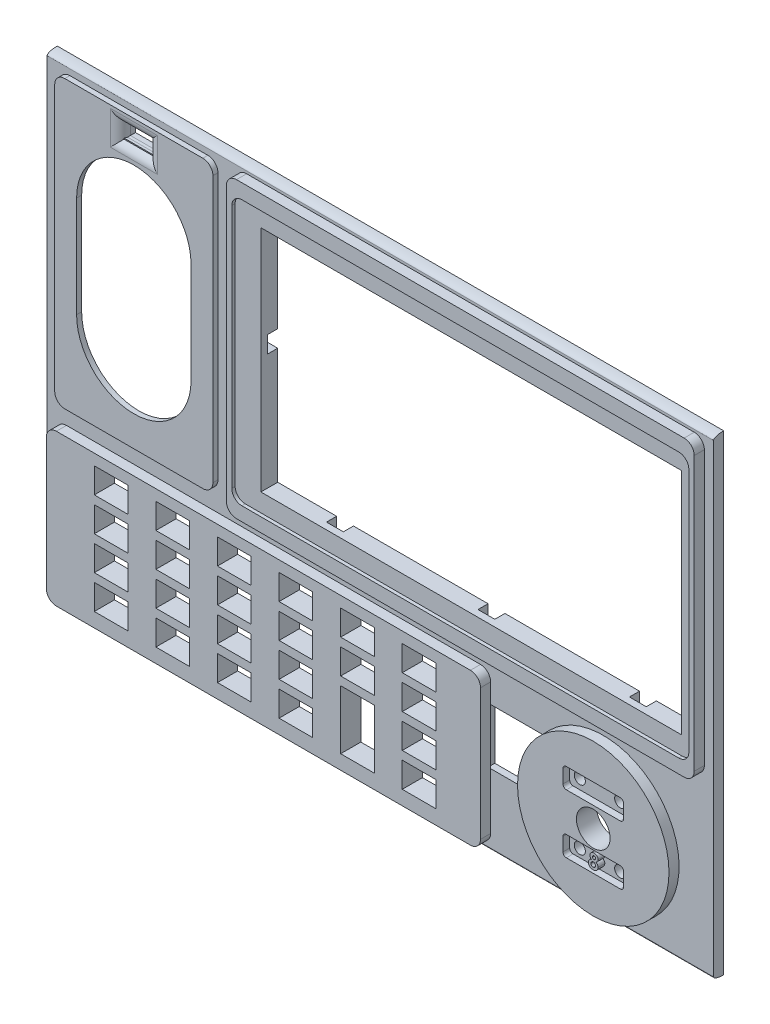
SolidWorks part; units mm, degrees
ref_plane "Front Plane" through (0, 0, 0) normal (0, 0, 1) x (1, 0, 0)
ref_plane "Top Plane" through (0, 0, 0) normal (0, 1, 0) x (1, 0, 0)
ref_plane "Right Plane" through (0, 0, 0) normal (1, 0, 0) x (0, 0, -1)
sketch "Sketch1" plane through (0, 0, 0) normal (0, 0, 1) x (1, 0, 0)
  line L1 (99, -70) -> (-99, -70)
  line L2 (99, -70) -> (99, 70)
  line L3 (99, 70) -> (-99, 70)
  line L4 (-99, -70) -> (-99, 70)
  line L5 (99, -70) -> (-99, 70) construction
  line L6 (99, 70) -> (-99, -70) construction
  point P0 (0, 0)
  dimension "D1" = 198
  dimension "D2" = 140
extrude "main_body" add sketch "Sketch1" along normal blind 3
fillet "long_corners" radius 3 2 edges at (0, 70, 3) (0, -70, 3) second distance 1 first distance on face at (0, 70, 1.5) first distance on face at (0, -70, 1.5)
sketch "Sketch2" plane through (0, 0, 3) normal (0, 0, 1) x (1, 0, 0)
  line L0 (-99, 24.75) -> (99, 24.75) construction
  line L1 (-99, 69) -> (-99, -69) construction
  line L2 (99, -69) -> (99, 69) construction
  line L3 (99, 69) -> (-99, 69) construction
  line L4 (-48.25, -17.75) -> (-95.25, -17.75)
  line L5 (-48.25, -17.75) -> (-48.25, 67.25)
  line L6 (-48.25, 67.25) -> (-95.25, 67.25)
  line L7 (-95.25, -17.75) -> (-95.25, 67.25)
  line L8 (-48.25, -17.75) -> (-95.25, 67.25) construction
  line L9 (-48.25, 67.25) -> (-95.25, -17.75) construction
  point P6 (-71.75, 24.75)
  dimension "D1" = 85
  dimension "D2" = 47
  dimension "D3" = 27.25
  dimension "D4" = 44.25
extrude "speaker" add sketch "Sketch2" along normal blind 1.5
fillet "speaker_corners" radius 3 4 edges at (-95.25, 67.25, 3.75) (-95.25, -17.75, 3.75) (-48.25, -17.75, 3.75) (-48.25, 67.25, 3.75)
sketch "Sketch19" plane through (0, 0, 4.5) normal (0, 0, 1) x (1, 0, 0)
  line L0 (-71.75, 67.25) -> (-71.75, -17.75) construction
  line L1 (-51.25, 67.25) -> (-92.25, 67.25) construction
  line L2 (-92.25, -17.75) -> (-51.25, -17.75) construction
  line L3 (-71.75, 8.25) -> (-71.75, 38.25) construction
  line L4 (-95.25, 64.25) -> (-95.25, -14.75) construction
  line L5 (-95.25, 24.75) -> (-48.25, 24.75) construction
  line L6 (-48.25, -14.75) -> (-48.25, 64.25) construction
  line L7 (-88.75, 8.25) -> (-88.75, 38.25)
  line L8 (-54.75, 8.25) -> (-54.75, 38.25)
  arc A0 (-88.75, 8.25) -> (-54.75, 8.25) centre (-71.75, 8.25) ccw
  arc A1 (-54.75, 38.25) -> (-88.75, 38.25) centre (-71.75, 38.25) ccw
  point P14 (-71.75, 23.25)
  point P19 (-71.75, -8.75)
  point P20 (-71.75, 55.25)
  dimension "D2" = 64
  dimension "D1" = 34
  dimension "D3" = 12
extrude "speaker_cut" cut sketch "Sketch19" against normal through all
sketch "Sketch21" plane through (0, 0, 0) normal (0, 0, -1) x (-1, 0, 0)
  line L0 (71.75, -8.75) -> (71.75, 55.25) construction
  line L2 (54.75, 8.25) -> (54.75, 38.25) construction
  line L3 (54.75, 23.25) -> (88.75, 23.25) construction
  line L4 (88.75, 38.25) -> (88.75, 8.25) construction
  line L5 (50.25, 59.25) -> (93.25, 59.25)
  line L6 (50.25, 59.25) -> (50.25, -12.75)
  line L7 (50.25, -12.75) -> (93.25, -12.75)
  line L8 (93.25, 59.25) -> (93.25, -12.75)
  line L9 (50.25, 59.25) -> (93.25, -12.75) construction
  line L10 (50.25, -12.75) -> (93.25, 59.25) construction
  arc A0 (54.75, 8.25) -> (88.75, 8.25) centre (71.75, 8.25) ccw construction
  arc A1 (88.75, 38.25) -> (54.75, 38.25) centre (71.75, 38.25) ccw construction
  point P14 (71.75, 23.25)
  dimension "D1" = 43
  dimension "D2" = 72
extrude "speaker_slot" cut sketch "Sketch21" against normal blind 3
sketch "Sketch36" plane through (0, 0, 3) normal (0, 0, -1) x (-1, 0, 0)
  line L0 (50.25, 23.25) -> (93.25, 23.25) construction
  line L1 (50.25, 59.25) -> (50.25, -12.75) construction
  line L2 (71.75, 8.2639) -> (71.75, 38.2361) construction
  line L3 (71.75, 8.2639) -> (71.75, 38.2361) construction
  line L4 (93.25, -12.75) -> (93.25, 59.25) construction
  line L5 (50.25, 59.25) -> (50.25, -12.75) construction
  line L6 (54.8316, 8.2639) -> (54.8316, 38.2361)
  line L9 (88.6684, 8.2639) -> (88.6684, 38.2361)
  line L10 (54.25, 8.2639) -> (54.25, 38.2361)
  line L11 (89.25, 8.2639) -> (89.25, 38.2361)
  line L12 (93.25, 59.25) -> (50.25, 59.25) construction
  line L13 (71.75, 59.25) -> (71.75, -12.75) construction
  line L14 (50.25, -12.75) -> (93.25, -12.75) construction
  line L23 (50.25, 57.25) -> (93.25, 57.25)
  line L25 (50.25, 57.25) -> (50.25, 56.75)
  line L26 (93.25, -0.25) -> (87.75, -0.25)
  line L27 (50.25, 56.75) -> (93.25, 56.75)
  line L28 (93.25, 57.25) -> (93.25, 56.75)
  line L37 (93.25, -12.75) -> (93.25, 59.25) construction
  line L38 (93.25, -0.25) -> (93.25, 0.25)
  line L39 (93.25, 0.25) -> (87.75, 0.25)
  line L48 (93.25, -10.75) -> (50.25, -10.75)
  line L49 (93.25, -10.75) -> (93.25, -10.25)
  line L50 (93.25, -10.25) -> (50.25, -10.25)
  line L51 (50.25, -10.75) -> (50.25, -10.25)
  line L52 (93.25, 46.75) -> (87.75, 46.75)
  line L53 (93.25, 46.75) -> (93.25, 46.25)
  line L54 (93.25, 46.25) -> (87.75, 46.25)
  line L55 (87.75, 46.75) -> (87.75, 46.25)
  line L56 (93.25, 35.25) -> (89.75, 35.25)
  line L57 (93.25, 35.25) -> (93.25, 34.75)
  line L58 (93.25, 34.75) -> (89.75, 34.75)
  line L59 (89.75, 35.25) -> (89.75, 34.75)
  line L60 (93.25, 23.25) -> (89.75, 23.25)
  line L61 (93.25, 23.25) -> (93.25, 23.75)
  line L62 (93.25, 23.75) -> (89.75, 23.75)
  line L63 (89.75, 23.25) -> (89.75, 23.75)
  line L64 (93.25, 10.75) -> (89.75, 10.75)
  line L65 (93.25, 10.75) -> (93.25, 11.25)
  line L66 (93.25, 11.25) -> (89.75, 11.25)
  line L67 (89.75, 10.75) -> (89.75, 11.25)
  line L68 (87.75, -0.25) -> (87.75, 0.25)
  line L69 (93.25, -5.25) -> (83.25, -5.25)
  line L70 (93.25, -5.25) -> (93.25, -5.75)
  line L71 (93.25, -5.75) -> (83.25, -5.75)
  line L72 (83.25, -5.25) -> (83.25, -5.75)
  line L73 (93.25, 52.25) -> (83.25, 52.25)
  line L74 (93.25, 52.25) -> (93.25, 51.75)
  line L75 (93.25, 51.75) -> (83.25, 51.75)
  line L76 (83.25, 52.25) -> (83.25, 51.75)
  line L77 (50.25, 52.25) -> (60.25, 52.25)
  line L78 (50.25, 52.25) -> (50.25, 51.75)
  line L79 (50.25, 51.75) -> (60.25, 51.75)
  line L80 (60.25, 52.25) -> (60.25, 51.75)
  line L81 (50.25, 46.75) -> (55.75, 46.75)
  line L82 (50.25, 46.75) -> (50.25, 46.25)
  line L83 (50.25, 46.25) -> (55.75, 46.25)
  line L84 (55.75, 46.75) -> (55.75, 46.25)
  line L85 (50.25, 35.25) -> (53.75, 35.25)
  line L86 (50.25, 35.25) -> (50.25, 34.75)
  line L87 (50.25, 34.75) -> (53.75, 34.75)
  line L88 (53.75, 35.25) -> (53.75, 34.75)
  line L89 (50.25, 23.25) -> (53.75, 23.25)
  line L90 (50.25, 23.25) -> (50.25, 23.75)
  line L91 (50.25, 23.75) -> (53.75, 23.75)
  line L92 (53.75, 23.25) -> (53.75, 23.75)
  line L93 (50.25, 10.25) -> (53.75, 10.25)
  line L94 (50.25, 10.25) -> (50.25, 10.75)
  line L95 (50.25, 10.75) -> (53.75, 10.75)
  line L96 (53.75, 10.25) -> (53.75, 10.75)
  line L97 (50.25, -0.25) -> (55.75, -0.25)
  line L98 (50.25, -0.25) -> (50.25, 0.25)
  line L99 (50.25, 0.25) -> (55.75, 0.25)
  line L100 (55.75, -0.25) -> (55.75, 0.25)
  line L101 (50.25, -5.25) -> (60.25, -5.25)
  line L102 (50.25, -5.25) -> (50.25, -5.75)
  line L103 (50.25, -5.75) -> (60.25, -5.75)
  line L104 (60.25, -5.25) -> (60.25, -5.75)
  arc A0 (54.25, 8.2639) -> (89.25, 8.2639) centre (71.75, 8.2639) ccw
  arc A1 (89.25, 38.2361) -> (54.25, 38.2361) centre (71.75, 38.2361) ccw
  arc A4 (54.8316, 8.2639) -> (88.6684, 8.2639) centre (71.75, 8.2639) ccw
  arc A5 (88.6684, 38.2361) -> (54.8316, 38.2361) centre (71.75, 38.2361) ccw
  point P6 (71.75, 23.25)
  point P22 (71.75, 23.25)
  point P31 (89.25, 23.25)
  point P32 (71.75, 55.1546)
  point P33 (71.75, -8.6546)
  point P95 (52, 35.25)
  point P96 (55.25, 51.75)
  point P97 (91.5, 10.75)
  dimension "D48" = 0.5816
  dimension "D1" = 33.8368
  dimension "D2" = 35
  dimension "D3" = 63.8091
  dimension "D4" = 0.5
  dimension "D5" = 0.5
  dimension "D6" = 0.5
  dimension "D7" = 0.5
  dimension "D8" = 0.5
  dimension "D9" = 11
  dimension "D10" = 11
  dimension "D11" = 5
  dimension "D12" = 4.5
  dimension "D13" = 10
  dimension "D14" = 5.5
  dimension "D15" = 3.5
  dimension "D16" = 3.5
  dimension "D17" = 0.5
  dimension "D18" = 0.5
  dimension "D19" = 0.5
  dimension "D20" = 0.5
  dimension "D21" = 11
  dimension "D22" = 11
  dimension "D23" = 5
  dimension "D24" = 10
  dimension "D25" = 5.5
  dimension "D26" = 3.5
  dimension "D27" = 3.5
  dimension "D28" = 0.5
  dimension "D29" = 0.5
  dimension "D30" = 0.5
  dimension "D31" = 0.5
  dimension "D32" = 0.5
  dimension "D33" = 0.5
  dimension "D34" = 0.5
  dimension "D35" = 12
  dimension "D36" = 10.5
  dimension "D37" = 5.5
  dimension "D38" = 5
  dimension "D39" = 4.5
  dimension "D40" = 3.5
  dimension "D41" = 10
  dimension "D42" = 4.5
  dimension "D43" = 5
  dimension "D44" = 10
  dimension "D45" = 3.5
  dimension "D46" = 5.5
  dimension "D47" = 10
extrude "speaker_print_support" [suppressed] add sketch "Sketch36" along normal blind 3
sketch "Sketch3" plane through (0, 0, 3) normal (0, 0, 1) x (1, 0, 0)
  line L0 (-99, 24.625) -> (99, 24.625) construction
  line L1 (-99, 69) -> (-99, -69) construction
  line L2 (99, -69) -> (99, 69) construction
  line L4 (-48.25, -14.75) -> (-48.25, 64.25) construction
  line L5 (96.25, -19) -> (-42.75, -19)
  line L6 (96.25, -19) -> (96.25, 68.25)
  line L7 (96.25, 68.25) -> (-42.75, 68.25)
  line L8 (-42.75, -19) -> (-42.75, 68.25)
  line L9 (96.25, -19) -> (-42.75, 68.25) construction
  line L10 (96.25, 68.25) -> (-42.75, -19) construction
  line L11 (99, 70) -> (-99, 70) construction
  point P8 (26.75, 24.625)
  dimension "D1" = 1.75
  dimension "D2" = 87.25
  dimension "D3" = 139
  dimension "D4" = 2.75
  dimension "D5" = 5.5
extrude "lcd" add sketch "Sketch3" along normal blind 3
fillet "lcd_corners" radius 3 4 edges at (96.25, -19, 4.5) (-42.75, -19, 4.5) (96.25, 68.25, 4.5) (-42.75, 68.25, 4.5)
sketch "Sketch9" plane through (0, 0, 6) normal (0, 0, 1) x (1, 0, 0)
  line L0 (-42.75, 24.5) -> (96.25, 24.5) construction
  line L1 (-42.75, 65.25) -> (-42.75, -16) construction
  line L2 (96.25, -16) -> (96.25, 65.25) construction
  line L3 (-39.75, -19) -> (93.25, -19) construction
  line L4 (94.65, -14.875) -> (-41.15, -14.875)
  line L5 (94.65, -14.875) -> (94.65, 63.875)
  line L6 (94.65, 63.875) -> (-41.15, 63.875)
  line L7 (-41.15, -14.875) -> (-41.15, 63.875)
  line L8 (94.65, -14.875) -> (-41.15, 63.875) construction
  line L9 (94.65, 63.875) -> (-41.15, -14.875) construction
  line L10 (93.25, 68.25) -> (-39.75, 68.25) construction
  line L11 (96.25, -16) -> (96.25, 65.25) construction
  point P6 (26.75, 24.5)
  dimension "D1" = 135.8
  dimension "D2" = 78.75
  dimension "D3" = 1.6
  dimension "D4" = 4.125
  dimension "D5" = 4.375
  dimension "D6" = 1.6
extrude "lcd_front" cut sketch "Sketch9" against normal blind 1
fillet "lcd_front_corners" radius 3 4 edges at (94.65, -14.875, 5.5) (94.65, 63.875, 5.5) (-41.15, 63.875, 5.5) (-41.15, -14.875, 5.5)
sketch "Sketch10" plane through (0, 0, 0) normal (0, 0, -1) x (-1, 0, 0)
  line L0 (-94.65, -11.875) -> (-94.65, 60.875) construction
  line L1 (-91.65, 63.875) -> (38.15, 63.875) construction
  line L2 (41.15, 63.875) -> (41.15, -14.875) construction
  line L3 (-94.65, 63.875) -> (41.15, 63.875) construction
  line L4 (33.5, -9.5) -> (-91.5, -9.5)
  line L5 (33.5, -9.5) -> (33.5, 58.5)
  line L6 (33.5, 58.5) -> (-91.5, 58.5)
  line L7 (-91.5, -9.5) -> (-91.5, 58.5)
  line L8 (-91.5, -9.5) -> (33.5, 58.5) construction
  line L9 (-91.5, 58.5) -> (33.5, -9.5) construction
  line L10 (-99, -70) -> (-99, 70) construction
  line L11 (-99, 70) -> (99, 70) construction
  line L13 (38.15, -14.875) -> (-91.65, -14.875) construction
  dimension "D1" = 125
  dimension "D2" = 68
  dimension "D3" = 7.5
  dimension "D4" = 7.65
  dimension "D5" = 11.5
  dimension "D6" = 5.375
  dimension "D7" = 3.15
  dimension "D8" = 5.375
  dimension "D9" = 5.375
extrude "lcd_back" cut sketch "Sketch10" against normal through all
sketch "Sketch56" plane through (0, 0, 0) normal (0, 0, -1) x (-1, 0, 0)
  line L0 (-91.5, -9.5) -> (33.5, -9.5) construction
  line L1 (-79, -9.5) -> (-74, -9.5)
  line L2 (-79, -9.5) -> (-79, -12.5)
  line L3 (-79, -12.5) -> (-74, -12.5)
  line L4 (-74, -9.5) -> (-74, -12.5)
  line L5 (33.5, 58.5) -> (-91.5, 58.5) construction
  line L6 (-34, -9.5) -> (-29, -9.5)
  line L7 (-34, -9.5) -> (-34, -12.5)
  line L8 (-34, -12.5) -> (-29, -12.5)
  line L9 (-29, -9.5) -> (-29, -12.5)
  line L10 (11, -9.5) -> (16, -9.5)
  line L11 (11, -9.5) -> (11, -12.5)
  line L12 (11, -12.5) -> (16, -12.5)
  line L13 (16, -9.5) -> (16, -12.5)
  line L14 (-79, 58.5) -> (-74, 58.5)
  line L15 (-79, 58.5) -> (-79, 61.5)
  line L16 (-79, 61.5) -> (-74, 61.5)
  line L17 (-74, 58.5) -> (-74, 61.5)
  line L18 (33.5, -9.5) -> (33.5, 58.5) construction
  line L19 (-34, 58.5) -> (-29, 58.5)
  line L20 (-34, 58.5) -> (-34, 61.5)
  line L21 (-34, 61.5) -> (-29, 61.5)
  line L22 (-29, 58.5) -> (-29, 61.5)
  line L23 (11, 58.5) -> (16, 58.5)
  line L24 (11, 58.5) -> (11, 61.5)
  line L25 (11, 61.5) -> (16, 61.5)
  line L26 (16, 58.5) -> (16, 61.5)
  line L27 (33.5, 30) -> (36.5, 30)
  line L28 (33.5, 30) -> (33.5, 25)
  line L29 (33.5, 25) -> (36.5, 25)
  line L30 (36.5, 30) -> (36.5, 25)
  line L31 (-99, -70) -> (-99, 70) construction
  line L32 (-99, 70) -> (99, 70) construction
  point P34 (-29, -11)
  dimension "D1" = 5
  dimension "D2" = 5
  dimension "D3" = 5
  dimension "D4" = 5
  dimension "D5" = 5
  dimension "D6" = 5
  dimension "D7" = 5
  dimension "D8" = 3
  dimension "D9" = 3
  dimension "D10" = 3
  dimension "D11" = 3
  dimension "D12" = 3
  dimension "D13" = 3
  dimension "D14" = 3
  dimension "D15" = 40
  dimension "D16" = 40
  dimension "D17" = 20
  dimension "D18" = 20
  dimension "D19" = 40
  dimension "D20" = 40
  dimension "D21" = 40
extrude "lcd_glue_points" cut sketch "Sketch56" against normal blind 3
sketch "Sketch4" plane through (0, 0, 3) normal (0, 0, 1) x (1, 0, 0)
  line L0 (-99, -45.75) -> (99, -45.75) construction
  line L1 (-99, 69) -> (-99, -69) construction
  line L2 (99, -69) -> (99, 69) construction
  line L4 (-92.25, -17.75) -> (-51.25, -17.75) construction
  line L5 (32.75, -68.25) -> (-96.25, -68.25)
  line L6 (32.75, -68.25) -> (32.75, -23.25)
  line L7 (32.75, -23.25) -> (-96.25, -23.25)
  line L8 (-96.25, -68.25) -> (-96.25, -23.25)
  line L9 (32.75, -68.25) -> (-96.25, -23.25) construction
  line L10 (32.75, -23.25) -> (-96.25, -68.25) construction
  line L11 (-99, -70) -> (99, -70) construction
  point P8 (-31.75, -45.75)
  dimension "D1" = 1.75
  dimension "D2" = 129
  dimension "D3" = 45
  dimension "D4" = 2.75
  dimension "D5" = 5.5
extrude "keypad" add sketch "Sketch4" along normal blind 3
fillet "keypad_corners" radius 3 4 edges at (-96.25, -68.25, 4.5) (32.75, -68.25, 4.5) (32.75, -23.25, 4.5) (-96.25, -23.25, 4.5)
sketch "Sketch25" plane through (0, 0, 6) normal (0, 0, 1) x (1, 0, 0)
  line L0 (-96.25, -30.25) -> (32.75, -30.25) construction
  line L1 (29.75, -23.25) -> (-93.25, -23.25) construction
  line L2 (-93.25, -68.25) -> (29.75, -68.25) construction
  line L3 (-77, -23.25) -> (-77, -68.25) construction
  line L5 (-35.4, -64) -> (32.75, -64) construction
  line L6 (-96.25, -26.25) -> (-96.25, -65.25) construction
  line L11 (32.75, -65.25) -> (32.75, -26.25) construction
  line L12 (-58.7, -23.25) -> (-58.7, -68.25) construction
  line L13 (-96.25, -40.25) -> (32.75, -40.25) construction
  line L14 (29.75, -23.25) -> (-93.25, -23.25) construction
  line L15 (-40.4, -23.25) -> (-40.4, -68.25) construction
  line L16 (-93.25, -68.25) -> (29.75, -68.25) construction
  line L17 (-72, -34) -> (-82, -34)
  line L18 (-22.1, -23.25) -> (-22.1, -68.25) construction
  line L19 (-96.25, -50.25) -> (32.75, -50.25) construction
  line L20 (-3.8, -23.25) -> (-3.8, -68.25) construction
  line L21 (-72, -34) -> (-72, -26.5)
  line L22 (14.5, -23.25) -> (14.5, -68.25) construction
  line L23 (-96.25, -26.25) -> (-96.25, -65.25) construction
  line L24 (-96.25, -60.25) -> (32.75, -60.25) construction
  line L25 (-72, -26.5) -> (-82, -26.5)
  line L26 (-82, -34) -> (-82, -26.5)
  line L27 (-72, -34) -> (-82, -26.5) construction
  line L28 (-72, -26.5) -> (-82, -34) construction
  line L29 (-72, -44) -> (-82, -44)
  line L30 (-72, -44) -> (-72, -36.5)
  line L31 (-72, -36.5) -> (-82, -36.5)
  line L32 (-82, -44) -> (-82, -36.5)
  line L33 (-72, -44) -> (-82, -36.5) construction
  line L34 (-72, -36.5) -> (-82, -44) construction
  line L35 (-72, -54) -> (-82, -54)
  line L36 (-72, -54) -> (-72, -46.5)
  line L37 (-72, -46.5) -> (-82, -46.5)
  line L38 (-82, -54) -> (-82, -46.5)
  line L39 (-72, -54) -> (-82, -46.5) construction
  line L40 (-72, -46.5) -> (-82, -54) construction
  line L41 (-72, -64) -> (-82, -64)
  line L42 (-72, -64) -> (-72, -56.5)
  line L43 (-72, -56.5) -> (-82, -56.5)
  line L44 (-82, -64) -> (-82, -56.5)
  line L45 (-72, -64) -> (-82, -56.5) construction
  line L46 (-72, -56.5) -> (-82, -64) construction
  line L47 (-53.7, -34) -> (-63.7, -34)
  line L48 (-53.7, -34) -> (-53.7, -26.5)
  line L49 (-53.7, -26.5) -> (-63.7, -26.5)
  line L50 (-63.7, -34) -> (-63.7, -26.5)
  line L51 (-53.7, -34) -> (-63.7, -26.5) construction
  line L52 (-53.7, -26.5) -> (-63.7, -34) construction
  line L53 (-53.7, -44) -> (-63.7, -44)
  line L54 (-53.7, -44) -> (-53.7, -36.5)
  line L55 (-53.7, -36.5) -> (-63.7, -36.5)
  line L56 (-63.7, -44) -> (-63.7, -36.5)
  line L57 (-53.7, -44) -> (-63.7, -36.5) construction
  line L58 (-53.7, -36.5) -> (-63.7, -44) construction
  line L59 (-53.7, -54) -> (-63.7, -54)
  line L60 (-53.7, -54) -> (-53.7, -46.5)
  line L61 (-53.7, -46.5) -> (-63.7, -46.5)
  line L62 (-63.7, -54) -> (-63.7, -46.5)
  line L63 (-53.7, -54) -> (-63.7, -46.5) construction
  line L64 (-53.7, -46.5) -> (-63.7, -54) construction
  line L65 (-53.7, -64) -> (-63.7, -64)
  line L66 (-53.7, -64) -> (-53.7, -56.5)
  line L67 (-53.7, -56.5) -> (-63.7, -56.5)
  line L68 (-63.7, -64) -> (-63.7, -56.5)
  line L69 (-53.7, -64) -> (-63.7, -56.5) construction
  line L70 (-53.7, -56.5) -> (-63.7, -64) construction
  line L71 (-35.4, -34) -> (-45.4, -34)
  line L72 (-35.4, -34) -> (-35.4, -26.5)
  line L73 (-35.4, -26.5) -> (-45.4, -26.5)
  line L74 (-45.4, -34) -> (-45.4, -26.5)
  line L75 (-35.4, -34) -> (-45.4, -26.5) construction
  line L76 (-35.4, -26.5) -> (-45.4, -34) construction
  line L77 (-35.4, -44) -> (-45.4, -44)
  line L78 (-35.4, -44) -> (-35.4, -36.5)
  line L79 (-35.4, -36.5) -> (-45.4, -36.5)
  line L80 (-45.4, -44) -> (-45.4, -36.5)
  line L81 (-35.4, -44) -> (-45.4, -36.5) construction
  line L82 (-35.4, -36.5) -> (-45.4, -44) construction
  line L83 (-35.4, -54) -> (-45.4, -54)
  line L84 (-35.4, -54) -> (-35.4, -46.5)
  line L85 (-35.4, -46.5) -> (-45.4, -46.5)
  line L86 (-45.4, -54) -> (-45.4, -46.5)
  line L87 (-35.4, -54) -> (-45.4, -46.5) construction
  line L88 (-35.4, -46.5) -> (-45.4, -54) construction
  line L89 (-35.4, -64) -> (-45.4, -64)
  line L90 (-35.4, -64) -> (-35.4, -56.5)
  line L91 (-35.4, -56.5) -> (-45.4, -56.5)
  line L92 (-45.4, -64) -> (-45.4, -56.5)
  line L93 (-35.4, -64) -> (-45.4, -56.5) construction
  line L94 (-35.4, -56.5) -> (-45.4, -64) construction
  line L95 (-17.1, -34) -> (-27.1, -34)
  line L96 (-17.1, -34) -> (-17.1, -26.5)
  line L97 (-17.1, -26.5) -> (-27.1, -26.5)
  line L98 (-27.1, -34) -> (-27.1, -26.5)
  line L99 (-17.1, -34) -> (-27.1, -26.5) construction
  line L100 (-17.1, -26.5) -> (-27.1, -34) construction
  line L101 (-17.1, -44) -> (-27.1, -44)
  line L102 (-17.1, -44) -> (-17.1, -36.5)
  line L103 (-17.1, -36.5) -> (-27.1, -36.5)
  line L104 (-27.1, -44) -> (-27.1, -36.5)
  line L105 (-17.1, -44) -> (-27.1, -36.5) construction
  line L106 (-17.1, -36.5) -> (-27.1, -44) construction
  line L111 (-17.1, -54) -> (-27.1, -54)
  line L112 (-17.1, -54) -> (-17.1, -46.5)
  line L113 (-17.1, -46.5) -> (-27.1, -46.5)
  line L114 (-27.1, -54) -> (-27.1, -46.5)
  line L115 (-17.1, -54) -> (-27.1, -46.5) construction
  line L116 (-17.1, -46.5) -> (-27.1, -54) construction
  line L117 (-17.1, -64) -> (-27.1, -64)
  line L118 (-17.1, -64) -> (-17.1, -56.5)
  line L119 (-17.1, -56.5) -> (-27.1, -56.5)
  line L120 (-27.1, -64) -> (-27.1, -56.5)
  line L121 (-17.1, -64) -> (-27.1, -56.5) construction
  line L122 (-17.1, -56.5) -> (-27.1, -64) construction
  line L127 (1.2, -34) -> (-8.8, -34)
  line L128 (1.2, -34) -> (1.2, -26.5)
  line L129 (1.2, -26.5) -> (-8.8, -26.5)
  line L130 (-8.8, -34) -> (-8.8, -26.5)
  line L131 (1.2, -34) -> (-8.8, -26.5) construction
  line L132 (1.2, -26.5) -> (-8.8, -34) construction
  line L133 (19.5, -34) -> (9.5, -34)
  line L134 (19.5, -34) -> (19.5, -26.5)
  line L135 (19.5, -26.5) -> (9.5, -26.5)
  line L136 (9.5, -34) -> (9.5, -26.5)
  line L137 (19.5, -34) -> (9.5, -26.5) construction
  line L138 (19.5, -26.5) -> (9.5, -34) construction
  line L139 (1.2, -44) -> (-8.8, -44)
  line L140 (1.2, -44) -> (1.2, -36.5)
  line L141 (1.2, -36.5) -> (-8.8, -36.5)
  line L142 (-8.8, -44) -> (-8.8, -36.5)
  line L143 (1.2, -44) -> (-8.8, -36.5) construction
  line L144 (1.2, -36.5) -> (-8.8, -44) construction
  line L145 (19.5, -44) -> (9.5, -44)
  line L146 (19.5, -44) -> (19.5, -36.5)
  line L147 (19.5, -36.5) -> (9.5, -36.5)
  line L148 (9.5, -44) -> (9.5, -36.5)
  line L149 (19.5, -44) -> (9.5, -36.5) construction
  line L150 (19.5, -36.5) -> (9.5, -44) construction
  line L151 (19.5, -54) -> (9.5, -54)
  line L152 (19.5, -54) -> (19.5, -46.5)
  line L153 (19.5, -46.5) -> (9.5, -46.5)
  line L154 (9.5, -54) -> (9.5, -46.5)
  line L155 (19.5, -54) -> (9.5, -46.5) construction
  line L156 (19.5, -46.5) -> (9.5, -54) construction
  line L157 (19.5, -64) -> (9.5, -64)
  line L158 (19.5, -64) -> (19.5, -56.5)
  line L159 (19.5, -56.5) -> (9.5, -56.5)
  line L160 (9.5, -64) -> (9.5, -56.5)
  line L161 (19.5, -64) -> (9.5, -56.5) construction
  line L162 (19.5, -56.5) -> (9.5, -64) construction
  line L163 (1.2, -64) -> (-8.8, -64)
  line L164 (1.2, -64) -> (1.2, -46.5)
  line L165 (1.2, -46.5) -> (-8.8, -46.5)
  line L166 (-8.8, -64) -> (-8.8, -46.5)
  line L167 (1.2, -64) -> (-8.8, -46.5) construction
  line L168 (1.2, -46.5) -> (-8.8, -64) construction
  point P34 (-77, -30.25)
  point P39 (-77, -40.25)
  point P44 (-77, -50.25)
  point P49 (-77, -60.25)
  point P54 (-58.7, -30.25)
  point P59 (-58.7, -40.25)
  point P64 (-58.7, -50.25)
  point P69 (-58.7, -60.25)
  point P74 (-40.4, -30.25)
  point P79 (-40.4, -40.25)
  point P84 (-40.4, -50.25)
  point P89 (-40.4, -60.25)
  point P94 (-22.1, -30.25)
  point P99 (-22.1, -40.25)
  point P104 (-22.1, -50.25)
  point P109 (-22.1, -60.25)
  point P114 (-3.8, -30.25)
  point P119 (14.5, -30.25)
  point P124 (-3.8, -40.25)
  point P129 (14.5, -40.25)
  point P134 (14.5, -50.25)
  point P139 (14.5, -60.25)
  point P144 (-3.8, -55.25)
  dimension "D1" = 18.25
  dimension "D2" = 18.3
  dimension "D3" = 18.3
  dimension "D4" = 18.3
  dimension "D5" = 18.3
  dimension "D6" = 18.3
  dimension "D7" = 19.25
  dimension "D8" = 7
  dimension "D9" = 10
  dimension "D10" = 10
  dimension "D11" = 10
  dimension "D12" = 8
  dimension "D13" = 10
  dimension "D14" = 10
  dimension "D15" = 10
  dimension "D16" = 10
  dimension "D17" = 10
  dimension "D18" = 10
  dimension "D19" = 10
  dimension "D20" = 10
  dimension "D21" = 10
  dimension "D22" = 10
  dimension "D23" = 10
  dimension "D24" = 10
  dimension "D25" = 10
  dimension "D26" = 10
  dimension "D27" = 10
  dimension "D28" = 10
  dimension "D29" = 10
  dimension "D30" = 10
  dimension "D31" = 10
  dimension "D32" = 10
  dimension "D33" = 10
  dimension "D34" = 10
  dimension "D35" = 10
  dimension "D36" = 7.5
  dimension "D37" = 7.5
  dimension "D38" = 7.5
  dimension "D39" = 7.5
  dimension "D40" = 7.5
  dimension "D41" = 7.5
  dimension "D42" = 17.5
  dimension "D43" = 7.5
  dimension "D44" = 7.5
  dimension "D45" = 7.5
  dimension "D46" = 7.5
  dimension "D47" = 7.5
  dimension "D48" = 7.5
  dimension "D49" = 7.5
  dimension "D50" = 7.5
  dimension "D51" = 7.5
  dimension "D52" = 7.5
  dimension "D53" = 7.5
  dimension "D54" = 7.5
  dimension "D55" = 7.5
  dimension "D56" = 7.5
  dimension "D57" = 7.5
  dimension "D58" = 7.5
  dimension "D59" = 5
extrude "keypad_cuts_0.8" cut sketch "Sketch25" against normal through all
sketch "Sketch40" plane through (0, 0, 6) normal (0, 0, 1) x (1, 0, 0)
  line L0 (16.75, -23.25) -> (16.75, -68.25) construction
  line L1 (-8.25, -23.25) -> (-8.25, -68.25) construction
  line L2 (-67.25, -23.25) -> (-67.25, -68.25) construction
  line L3 (-96.25, -45.75) -> (32.75, -45.75) construction
  line L4 (-83.25, -23.25) -> (-83.25, -68.25) construction
  line L5 (29.75, -23.25) -> (-93.25, -23.25) construction
  line L6 (-93.25, -68.25) -> (29.75, -68.25) construction
  line L11 (-77.25, -49.75) -> (-89.25, -49.75)
  line L12 (-77.25, -49.75) -> (-77.25, -41.75)
  line L13 (-93.25, -68.25) -> (29.75, -68.25) construction
  line L14 (-77.25, -41.75) -> (-89.25, -41.75)
  line L15 (-89.25, -49.75) -> (-89.25, -41.75)
  line L16 (-35.25, -68.25) -> (-35.25, -23.25) construction
  line L18 (29.75, -23.25) -> (-93.25, -23.25) construction
  line L19 (-77.25, -49.75) -> (-89.25, -41.75) construction
  line L20 (-51.25, -68.25) -> (-51.25, -23.25) construction
  line L22 (-77.25, -41.75) -> (-89.25, -49.75) construction
  line L23 (-61.25, -49.75) -> (-73.25, -49.75)
  line L24 (-61.25, -49.75) -> (-61.25, -41.75)
  line L25 (-61.25, -41.75) -> (-73.25, -41.75)
  line L26 (-73.25, -49.75) -> (-73.25, -41.75)
  line L27 (-61.25, -49.75) -> (-73.25, -41.75) construction
  line L28 (-61.25, -41.75) -> (-73.25, -49.75) construction
  line L29 (-45.25, -49.75) -> (-57.25, -49.75)
  line L30 (-45.25, -49.75) -> (-45.25, -41.75)
  line L31 (-45.25, -41.75) -> (-57.25, -41.75)
  line L32 (-57.25, -49.75) -> (-57.25, -41.75)
  line L33 (-45.25, -49.75) -> (-57.25, -41.75) construction
  line L34 (-45.25, -41.75) -> (-57.25, -49.75) construction
  line L35 (-29.25, -49.75) -> (-41.25, -49.75)
  line L36 (-29.25, -49.75) -> (-29.25, -41.75)
  line L37 (-29.25, -41.75) -> (-41.25, -41.75)
  line L38 (-41.25, -49.75) -> (-41.25, -41.75)
  line L39 (-29.25, -49.75) -> (-41.25, -41.75) construction
  line L40 (-29.25, -41.75) -> (-41.25, -49.75) construction
  line L45 (-2.25, -41.75) -> (-14.25, -41.75)
  line L46 (-2.25, -41.75) -> (-2.25, -33.75)
  line L51 (-2.25, -33.75) -> (-14.25, -33.75)
  line L52 (-14.25, -41.75) -> (-14.25, -33.75)
  line L53 (22.75, -35.75) -> (10.75, -35.75)
  line L54 (22.75, -35.75) -> (22.75, -27.75)
  line L55 (22.75, -27.75) -> (10.75, -27.75)
  line L56 (10.75, -35.75) -> (10.75, -27.75)
  line L57 (22.75, -35.75) -> (10.75, -27.75) construction
  line L58 (22.75, -27.75) -> (10.75, -35.75) construction
  line L59 (22.75, -63.75) -> (10.75, -63.75)
  line L60 (22.75, -63.75) -> (22.75, -55.75)
  line L61 (22.75, -55.75) -> (10.75, -55.75)
  line L62 (10.75, -63.75) -> (10.75, -55.75)
  line L63 (22.75, -63.75) -> (10.75, -55.75) construction
  line L64 (22.75, -55.75) -> (10.75, -63.75) construction
  line L69 (32.75, -65.25) -> (32.75, -26.25) construction
  line L70 (-2.25, -57.25) -> (-14.25, -57.25)
  line L75 (-2.25, -57.25) -> (-2.25, -49.25)
  line L76 (-2.25, -49.25) -> (-14.25, -49.25)
  line L77 (-2.25, -41.75) -> (-14.25, -33.75) construction
  line L78 (-2.25, -33.75) -> (-14.25, -41.75) construction
  line L85 (-14.25, -57.25) -> (-14.25, -49.25)
  line L86 (-2.25, -57.25) -> (-14.25, -49.25) construction
  line L87 (-2.25, -49.25) -> (-14.25, -57.25) construction
  line L88 (-96.25, -26.25) -> (-96.25, -65.25) construction
  line L89 (32.75, -65.25) -> (32.75, -26.25) construction
  line L93 (32.75, -59.75) -> (-96.25, -59.75) construction
  line L94 (-96.25, -31.75) -> (32.75, -31.75) construction
  line L95 (32.75, -31.75) -> (32.75, -37.75) construction
  line L96 (32.75, -37.75) -> (-96.25, -37.75) construction
  line L99 (-96.25, -26.25) -> (-96.25, -65.25) construction
  line L100 (-96.25, -53.75) -> (32.75, -53.75) construction
  point P18 (-83.25, -45.75)
  point P25 (-67.25, -45.75)
  point P30 (-51.25, -45.75)
  point P35 (-35.25, -45.75)
  point P40 (-8.25, -37.75)
  point P45 (-8.25, -53.25)
  point P50 (16.75, -31.75)
  point P55 (16.75, -59.75)
  dimension "D1" = 8
  dimension "D2" = 8
  dimension "D3" = 8
  dimension "D4" = 8
  dimension "D5" = 8
  dimension "D6" = 12
  dimension "D7" = 8
  dimension "D8" = 8
  dimension "D9" = 12
  dimension "D10" = 12
  dimension "D11" = 12
  dimension "D12" = 12
  dimension "D13" = 12
  dimension "D14" = 12
  dimension "D15" = 8
  dimension "D16" = 12
  dimension "D17" = 8
  dimension "D18" = 8
  dimension "D19" = 27
  dimension "D20" = 14
  dimension "D21" = 16
  dimension "D22" = 16
  dimension "D23" = 16
  dimension "D24" = 25
  dimension "D25" = 14
extrude "keypad_cuts_0.7" [suppressed] cut sketch "Sketch40" against normal through all
sketch "Sketch41" [suppressed] plane through (0, 0, 0) normal (0, 0, -1) x (-1, 0, 0)
  line L0 (-22.75, -27.75) -> (-10.75, -35.75) construction
  line L1 (-22.75, -55.75) -> (-10.75, -63.75) construction
  line L2 (8.25, -33.75) -> (8.25, -57.25) construction
  line L3 (-10.75, -63.75) -> (-22.75, -63.75) construction
  line L4 (29.25, -45.75) -> (89.25, -45.75) construction
  line L5 (29.25, -49.75) -> (29.25, -41.75) construction
  line L6 (89.25, -41.75) -> (89.25, -49.75) construction
  line L7 (-6.75, -39.75) -> (-26.75, -39.75)
  line L8 (2.25, -33.75) -> (14.25, -33.75) construction
  line L9 (-6.75, -39.75) -> (-6.75, -23.75)
  line L10 (91.25, -52.75) -> (27.25, -52.75)
  line L11 (-6.75, -23.75) -> (-26.75, -23.75)
  line L12 (14.25, -57.25) -> (2.25, -57.25) construction
  line L13 (-26.75, -39.75) -> (-26.75, -23.75)
  line L14 (-10.75, -55.75) -> (-22.75, -63.75) construction
  line L15 (-6.75, -39.75) -> (-26.75, -23.75) construction
  line L16 (-10.75, -35.75) -> (-22.75, -35.75) construction
  line L17 (-22.75, -35.75) -> (-22.75, -27.75) construction
  line L18 (-22.75, -35.75) -> (-10.75, -27.75) construction
  line L19 (-6.75, -23.75) -> (-26.75, -39.75) construction
  line L21 (-6.75, -67.75) -> (-26.75, -67.75)
  line L22 (16.25, -59.5) -> (0.25, -59.5)
  line L23 (-6.75, -67.75) -> (-6.75, -51.75)
  line L24 (91.25, -52.75) -> (91.25, -38.75)
  line L25 (-6.75, -51.75) -> (-26.75, -51.75)
  line L26 (91.25, -38.75) -> (27.25, -38.75)
  line L27 (-26.75, -67.75) -> (-26.75, -51.75)
  line L28 (27.25, -52.75) -> (27.25, -38.75)
  line L29 (-6.75, -67.75) -> (-26.75, -51.75) construction
  line L30 (91.25, -52.75) -> (27.25, -38.75) construction
  line L31 (-6.75, -51.75) -> (-26.75, -67.75) construction
  line L36 (16.25, -59.5) -> (16.25, -31.5)
  line L37 (16.25, -31.5) -> (0.25, -31.5)
  line L42 (0.25, -59.5) -> (0.25, -31.5)
  line L43 (16.25, -59.5) -> (0.25, -31.5) construction
  line L48 (91.25, -38.75) -> (27.25, -52.75) construction
  line L49 (16.25, -31.5) -> (0.25, -59.5) construction
  point P19 (59.25, -45.75)
  point P44 (8.25, -45.5)
  point P68 (-16.75, -59.75)
  point P69 (-16.75, -31.75)
  dimension "D1" = 20
  dimension "D2" = 20
  dimension "D3" = 16
  dimension "D4" = 16
  dimension "D5" = 16
  dimension "D6" = 28
  dimension "D7" = 64
  dimension "D8" = 14
extrude "keypad_back_0.7" [suppressed] cut sketch "Sketch41" against normal blind 5
sketch "Sketch5" plane through (0, 0, 3) normal (0, 0, 1) x (1, 0, 0)
  line L0 (32.75, -45.75) -> (99, -45.75) construction
  line L1 (32.75, -65.25) -> (32.75, -26.25) construction
  line L2 (99, -69) -> (99, 69) construction
  circle A0 centre (66.25, -45.75) radius 22.5
  dimension "D1" = 45
  dimension "D2" = 32.75
  dimension "D3" = 33.5
extrude "vfo" add sketch "Sketch5" along normal blind 3
sketch "Sketch7" plane through (0, 0, 6) normal (0, 0, 1) x (1, 0, 0)
  line L0 (43.75, -45.75) -> (88.75, -45.75) construction
  line L1 (66.25, -23.25) -> (66.25, -68.25) construction
  circle A0 centre (66.25, -45.75) radius 22.5 construction
  circle A1 centre (66.25, -45.75) radius 22.5 construction
  circle A2 centre (66.25, -45.75) radius 5
  dimension "D1" = 10
extrude "vfo_encoder_knob_cut" cut sketch "Sketch7" against normal through all
sketch "Sketch37" plane through (0, 0, 6) normal (0, 0, 1) x (1, 0, 0)
  line L1 (57.25, -51.25) -> (75.25, -51.25)
  line L2 (57.25, -51.25) -> (57.25, -57.25)
  line L3 (57.25, -57.25) -> (75.25, -57.25)
  line L4 (75.25, -51.25) -> (75.25, -57.25)
  line L5 (57.25, -33.75) -> (75.25, -33.75)
  line L6 (57.25, -33.75) -> (57.25, -39.75)
  line L7 (57.25, -39.75) -> (75.25, -39.75)
  line L8 (75.25, -33.75) -> (75.25, -39.75)
  circle A0 centre (66.25, -45.75) radius 5 construction
  dimension "D1" = 6
  dimension "D2" = 18
  dimension "D3" = 5.5
  dimension "D4" = 9
  dimension "D5" = 18
  dimension "D6" = 6
  dimension "D7" = 6
  dimension "D8" = 9
extrude "logo_cut" cut sketch "Sketch37" against normal blind 2
sketch "Sketch44" plane through (0, 0, 6) normal (0, 0, 1) x (1, 0, 0)
  line L0 (66.25, -23.25) -> (66.25, -68.25) construction
  line L3 (43.75, -45.75) -> (88.75, -45.75) construction
  line L6 (66.25, -36.75) -> (72.25, -36.75) construction
  line L7 (66.25, -54.75) -> (72.25, -54.75) construction
  line L9 (60.25, -36.75) -> (66.25, -36.75) construction
  line L11 (60.25, -54.75) -> (66.25, -54.75) construction
  circle A0 centre (66.25, -45.75) radius 22.5 construction
  circle A1 centre (66.25, -45.75) radius 22.5 construction
  circle A4 centre (60.25, -36.75) radius 1.65
  circle A5 centre (72.25, -36.75) radius 1.65
  circle A6 centre (60.25, -54.75) radius 1.65
  circle A7 centre (72.25, -54.75) radius 1.65
  dimension "D9" = 3.3
  dimension "D10" = 3.3
  dimension "D11" = 3.3
  dimension "D12" = 3.3
  dimension "D7" = 9
  dimension "D8" = 9
  dimension "D13" = 6
  dimension "D14" = 6
  dimension "D15" = 6
  dimension "D16" = 6
extrude "encoder_mount_holes" cut sketch "Sketch44" against normal through all
fillet "enc_cut_corners" radius 1 8 edges at (57.25, -57.25, 5) (75.25, -57.25, 5) (75.25, -51.25, 5) (57.25, -51.25, 5) (57.25, -39.75, 5) (75.25, -39.75, 5) (75.25, -33.75, 5) (57.25, -33.75, 5)
sketch "Sketch39" plane through (0, 0, 4) normal (0, 0, 1) x (1, 0, 0)
  line L0 (57.25, -52.25) -> (57.25, -56.25) construction
  line L1 (58.25, -57.25) -> (74.25, -57.25) construction
  text T0 "8" font "Century Gothic" height in points 16
  dimension "D1" = 7.5
  dimension "D2" = 1
extrude "logo_txt_ver" add sketch "Sketch39" along normal blind 2
sketch "esp32" plane through (0, 0, 0) normal (0, 0, -1) x (-1, 0, 0)
  line L0 (99, -70) -> (-99, -70) construction
  line L1 (-50.5, -32.05) -> (-32, -32.05)
  line L2 (-50.5, -32.05) -> (-50.5, -48.55)
  line L3 (-50.5, -48.55) -> (-32, -48.55)
  line L4 (-32, -32.05) -> (-32, -48.55)
  line L5 (-99, -70) -> (-99, 70) construction
  dimension "D1" = 21.45
  dimension "D2" = 48.5
  dimension "D3" = 16.5
  dimension "D4" = 18.5
extrude "esp32_can_cut" cut sketch "esp32" against normal blind 3
sketch "Sketch43" plane through (0, 0, 0) normal (0, 0, -1) x (-1, 0, 0)
  line L0 (99, -70) -> (-99, -70) construction
  line L1 (-23.5, -50.5) -> (-41, -50.5)
  line L2 (-23.5, -50.5) -> (-23.5, -68)
  line L3 (-23.5, -68) -> (-41, -68)
  line L4 (-41, -50.5) -> (-41, -68)
  line L5 (-99, -70) -> (-99, 70) construction
  dimension "D1" = 17.5
  dimension "D2" = 17.5
  dimension "D3" = 2
  dimension "D4" = 58
extrude "lora_cut" cut sketch "Sketch43" against normal blind 2.5
fillet "rf_corners" [suppressed] radius 1
sketch "Sketch47" plane through (0, 0, 0) normal (0, 0, -1) x (-1, 0, 0)
  line L0 (-50.5, -48.55) -> (-32, -48.55) construction
  line L1 (-31, -49.55) -> (-58, -49.55)
  line L2 (-31, -49.55) -> (-31, -31.05)
  line L3 (-31, -31.05) -> (-58, -31.05)
  line L4 (-58, -49.55) -> (-58, -31.05)
  line L5 (-31, -49.55) -> (-58, -31.05) construction
  line L6 (-31, -31.05) -> (-58, -49.55) construction
  line L7 (-50.5, -32.05) -> (-50.5, -48.55) construction
  point P0 (-44.5, -40.3)
  dimension "D1" = 27
  dimension "D2" = 18.5
  dimension "D3" = 1
  dimension "D4" = 7.5
extrude "esp32_ex_cut" cut sketch "Sketch47" against normal blind 1
sketch "Sketch49" plane through (0, 0, 0) normal (0, 0, -1) x (-1, 0, 0)
  line L0 (71.75, 59.25) -> (71.75, 70) construction
  line L1 (93.25, 59.25) -> (50.25, 59.25) construction
  line L2 (-99, 70) -> (99, 70) construction
  line L4 (75.75, 59.35) -> (67.75, 59.35)
  line L5 (75.75, 59.35) -> (75.75, 63.35)
  line L6 (75.75, 63.35) -> (67.75, 63.35)
  line L7 (67.75, 59.35) -> (67.75, 63.35)
  line L8 (75.75, 59.35) -> (67.75, 63.35) construction
  line L9 (75.75, 63.35) -> (67.75, 59.35) construction
  point P6 (71.75, 61.35)
  dimension "D1" = 8
  dimension "D2" = 4
  dimension "D3" = 0.1
extrude "amb_sensor" cut sketch "Sketch49" against normal through all
fillet "amb_corners" radius 3 4 edges at (-67.75, 61.35, 4.5) (-71.75, 63.35, 4.5) (-75.75, 61.35, 4.5) (-71.75, 59.35, 4.5)
sketch "Sketch50" plane through (0, 0, 6) normal (0, 0, 1) x (1, 0, 0)
  line L0 (-96.25, -45.1902) -> (-96.25, -45.25) construction
  line L1 (-96.25, -26.25) -> (-96.25, -65.25) construction
  line L2 (-96.25, -40.25) -> (32.75, -40.25) construction
  line L3 (-67.75, -23.25) -> (-67.75, -68.25) construction
  line L4 (29.75, -23.25) -> (-93.25, -23.25) construction
  line L5 (-93.25, -68.25) -> (29.75, -68.25) construction
  line L6 (-31.25, -23.25) -> (-31.25, -68.25) construction
  line L7 (29.75, -23.25) -> (-93.25, -23.25) construction
  line L8 (-49.5, -23.25) -> (-49.5, -68.25) construction
  line L9 (5.25, -23.25) -> (5.25, -68.25) construction
  line L10 (-13, -23.25) -> (-13, -68.25) construction
  line L11 (-96.25, -26.25) -> (-96.25, -65.25) construction
  line L12 (-96.25, -45.25) -> (32.75, -45.25) construction
  line L13 (32.75, -65.25) -> (32.75, -26.25) construction
  line L14 (9.5, -36.5) -> (9.5, -44) construction
  line L15 (-70, -46) -> (-84, -46)
  line L16 (-70, -46) -> (-70, -44.5)
  line L17 (-70, -44.5) -> (-84, -44.5)
  line L18 (-84, -46) -> (-84, -44.5)
  line L19 (-70, -46) -> (-84, -44.5) construction
  line L20 (-70, -44.5) -> (-84, -46) construction
  line L21 (-51.7, -46) -> (-65.7, -46)
  line L22 (-51.7, -46) -> (-51.7, -44.5)
  line L23 (-51.7, -44.5) -> (-65.7, -44.5)
  line L24 (-65.7, -46) -> (-65.7, -44.5)
  line L25 (-51.7, -46) -> (-65.7, -44.5) construction
  line L26 (-51.7, -44.5) -> (-65.7, -46) construction
  line L27 (-33.4, -46) -> (-47.4, -46)
  line L28 (-33.4, -46) -> (-33.4, -44.5)
  line L29 (-33.4, -44.5) -> (-47.4, -44.5)
  line L30 (-47.4, -46) -> (-47.4, -44.5)
  line L31 (-33.4, -46) -> (-47.4, -44.5) construction
  line L32 (-33.4, -44.5) -> (-47.4, -46) construction
  line L33 (-15.1, -46) -> (-29.1, -46)
  line L34 (-15.1, -46) -> (-15.1, -44.5)
  line L35 (-15.1, -44.5) -> (-29.1, -44.5)
  line L36 (-29.1, -46) -> (-29.1, -44.5)
  line L37 (-15.1, -46) -> (-29.1, -44.5) construction
  line L38 (-15.1, -44.5) -> (-29.1, -46) construction
  line L39 (3.2, -46) -> (-10.8, -46)
  line L40 (3.2, -46) -> (3.2, -44.5)
  line L41 (3.2, -44.5) -> (-10.8, -44.5)
  line L42 (-10.8, -46) -> (-10.8, -44.5)
  line L43 (3.2, -46) -> (-10.8, -44.5) construction
  line L44 (3.2, -44.5) -> (-10.8, -46) construction
  line L45 (21.5, -46) -> (7.5, -46)
  line L46 (21.5, -46) -> (21.5, -44.5)
  line L47 (21.5, -44.5) -> (7.5, -44.5)
  line L48 (7.5, -46) -> (7.5, -44.5)
  line L49 (21.5, -46) -> (7.5, -44.5) construction
  line L50 (21.5, -44.5) -> (7.5, -46) construction
  line L51 (-8.8, -36.5) -> (-8.8, -44) construction
  line L52 (-27.1, -36.5) -> (-27.1, -44) construction
  line L53 (-45.4, -36.5) -> (-45.4, -44) construction
  line L54 (-63.7, -36.5) -> (-63.7, -44) construction
  line L55 (-82, -36.5) -> (-82, -44) construction
  line L56 (1.2, -64) -> (1.2, -46.5) construction
  line L57 (7.49, -40.25) -> (8.99, -40.25)
  line L58 (32.75, -65.25) -> (32.75, -48.55) construction
  line L59 (32.75, -50.25) -> (-96.25, -50.25) construction
  line L60 (7.49, -40.25) -> (7.49, -44.49)
  line L61 (7.49, -44.49) -> (8.99, -44.49)
  line L62 (8.99, -40.25) -> (8.99, -44.49)
  line L63 (3.2, -50.25) -> (1.7, -50.25)
  line L64 (3.2, -50.25) -> (3.2, -46.01)
  line L65 (3.2, -46.01) -> (1.7, -46.01)
  line L66 (1.7, -50.25) -> (1.7, -46.01)
  line L67 (4.52, -40.25) -> (6.02, -40.25)
  line L68 (4.52, -40.25) -> (4.52, -50.25)
  line L69 (4.52, -50.25) -> (6.02, -50.25)
  line L70 (6.02, -40.25) -> (6.02, -50.25)
  line L71 (3.21, -50.25) -> (4.51, -50.25)
  line L72 (3.21, -50.25) -> (3.21, -48.75)
  line L73 (3.21, -48.75) -> (4.51, -48.75)
  line L74 (4.51, -50.25) -> (4.51, -48.75)
  line L75 (6.03, -40.25) -> (7.48, -40.25)
  line L76 (6.03, -40.25) -> (6.03, -41.75)
  line L77 (6.03, -41.75) -> (7.48, -41.75)
  line L78 (7.48, -40.25) -> (7.48, -41.75)
  line L79 (-72, -54) -> (-72, -46.5) construction
  line L80 (-13.78, -40.25) -> (-12.28, -40.25)
  line L81 (-13.78, -40.25) -> (-13.78, -50.25)
  line L82 (-13.78, -50.25) -> (-12.28, -50.25)
  line L83 (-12.28, -40.25) -> (-12.28, -50.25)
  line L84 (-31.88, -40.25) -> (-30.38, -40.25)
  line L85 (-31.88, -40.25) -> (-31.88, -50.25)
  line L86 (-31.88, -50.25) -> (-30.38, -50.25)
  line L87 (-30.38, -40.25) -> (-30.38, -50.25)
  line L88 (-50.23, -40.25) -> (-48.73, -40.25)
  line L89 (-50.23, -40.25) -> (-50.23, -50.25)
  line L90 (-50.23, -50.25) -> (-48.73, -50.25)
  line L91 (-48.73, -40.25) -> (-48.73, -50.25)
  line L92 (-68.53, -40.25) -> (-67.03, -40.25)
  line L93 (-68.53, -40.25) -> (-68.53, -50.25)
  line L94 (-68.53, -50.25) -> (-67.03, -50.25)
  line L95 (-67.03, -40.25) -> (-67.03, -50.25)
  line L96 (-70, -46.01) -> (-71.5, -46.01)
  line L97 (-70, -46.01) -> (-70, -50.25)
  line L98 (-70, -50.25) -> (-71.5, -50.25)
  line L99 (-71.5, -46.01) -> (-71.5, -50.25)
  line L100 (-69.99, -50.25) -> (-68.54, -50.25)
  line L101 (-69.99, -50.25) -> (-69.99, -48.75)
  line L102 (-69.99, -48.75) -> (-68.54, -48.75)
  line L103 (-68.54, -50.25) -> (-68.54, -48.75)
  line L104 (-53.7, -54) -> (-53.7, -46.5) construction
  line L105 (-67.02, -40.25) -> (-65.72, -40.25)
  line L106 (-67.02, -40.25) -> (-67.02, -41.75)
  line L107 (-67.02, -41.75) -> (-65.72, -41.75)
  line L108 (-65.72, -40.25) -> (-65.72, -41.75)
  line L109 (-65.71, -40.25) -> (-64.21, -40.25)
  line L110 (-65.71, -40.25) -> (-65.71, -44.49)
  line L111 (-65.71, -44.49) -> (-64.21, -44.49)
  line L112 (-64.21, -40.25) -> (-64.21, -44.49)
  line L113 (-51.7, -46.01) -> (-53.2, -46.01)
  line L114 (-51.7, -46.01) -> (-51.7, -50.25)
  line L115 (-51.7, -50.25) -> (-53.2, -50.25)
  line L116 (-53.2, -46.01) -> (-53.2, -50.25)
  line L117 (-51.69, -50.25) -> (-50.24, -50.25)
  line L118 (-51.69, -50.25) -> (-51.69, -48.75)
  line L119 (-51.69, -48.75) -> (-50.24, -48.75)
  line L120 (-50.24, -50.25) -> (-50.24, -48.75)
  line L121 (-48.72, -40.25) -> (-47.42, -40.25)
  line L122 (-48.72, -40.25) -> (-48.72, -41.75)
  line L123 (-48.72, -41.75) -> (-47.42, -41.75)
  line L124 (-47.42, -40.25) -> (-47.42, -41.75)
  line L125 (-47.41, -40.25) -> (-45.91, -40.25)
  line L126 (-47.41, -40.25) -> (-47.41, -44.49)
  line L127 (-47.41, -44.49) -> (-45.91, -44.49)
  line L128 (-45.91, -40.25) -> (-45.91, -44.49)
  line L129 (-33.4, -46.01) -> (-34.9, -46.01)
  line L130 (-33.4, -46.01) -> (-33.4, -50.25)
  line L131 (-33.4, -50.25) -> (-34.9, -50.25)
  line L132 (-34.9, -46.01) -> (-34.9, -50.25)
  line L133 (-33.39, -50.25) -> (-31.89, -50.25)
  line L134 (-33.39, -50.25) -> (-33.39, -48.75)
  line L135 (-33.39, -48.75) -> (-31.89, -48.75)
  line L136 (-31.89, -50.25) -> (-31.89, -48.75)
  line L137 (-30.37, -40.25) -> (-29.11, -40.25)
  line L138 (-30.37, -40.25) -> (-30.37, -41.75)
  line L139 (-30.37, -41.75) -> (-29.11, -41.75)
  line L140 (-29.11, -40.25) -> (-29.11, -41.75)
  line L141 (-29.1, -40.25) -> (-27.6, -40.25)
  line L142 (-29.1, -40.25) -> (-29.1, -44.49)
  line L143 (-29.1, -44.49) -> (-27.6, -44.49)
  line L144 (-27.6, -40.25) -> (-27.6, -44.49)
  line L145 (-15.1, -46.01) -> (-16.6, -46.01)
  line L146 (-15.1, -46.01) -> (-15.1, -50.25)
  line L147 (-15.1, -50.25) -> (-16.6, -50.25)
  line L148 (-16.6, -46.01) -> (-16.6, -50.25)
  line L149 (-15.09, -50.25) -> (-13.79, -50.25)
  line L150 (-15.09, -50.25) -> (-15.09, -48.75)
  line L151 (-15.09, -48.75) -> (-13.79, -48.75)
  line L152 (-13.79, -50.25) -> (-13.79, -48.75)
  line L153 (-12.27, -40.25) -> (-10.81, -40.25)
  line L154 (-12.27, -40.25) -> (-12.27, -41.75)
  line L155 (-12.27, -41.75) -> (-10.81, -41.75)
  line L156 (-10.81, -40.25) -> (-10.81, -41.75)
  line L157 (-10.8, -40.25) -> (-9.3, -40.25)
  line L158 (-10.8, -40.25) -> (-10.8, -44.49)
  line L159 (-10.8, -44.49) -> (-9.3, -44.49)
  line L160 (-9.3, -40.25) -> (-9.3, -44.49)
  line L161 (-35.4, -54) -> (-35.4, -46.5) construction
  line L162 (-17.1, -54) -> (-17.1, -46.5) construction
  point P22 (-77, -45.25)
  point P30 (-58.7, -45.25)
  point P35 (-40.4, -45.25)
  point P40 (-22.1, -45.25)
  point P45 (-3.8, -45.25)
  point P50 (14.5, -45.25)
  dimension "D1" = 18.25
  dimension "D2" = 18.25
  dimension "D3" = 18.25
  dimension "D4" = 18.25
  dimension "D5" = 28.5
  dimension "D6" = 22
  dimension "D7" = 1.5
  dimension "D8" = 14
  dimension "D9" = 5
  dimension "D10" = 1.5
  dimension "D11" = 14
  dimension "D12" = 5
  dimension "D13" = 1.5
  dimension "D14" = 14
  dimension "D15" = 5
  dimension "D16" = 1.5
  dimension "D17" = 14
  dimension "D18" = 5
  dimension "D19" = 1.5
  dimension "D20" = 14
  dimension "D21" = 5
  dimension "D22" = 1.5
  dimension "D23" = 14
  dimension "D24" = 5
  dimension "D25" = 5
  dimension "D26" = 5
  dimension "D27" = 0.01
  dimension "D28" = 0.01
  dimension "D29" = 1.5
  dimension "D30" = 1.5
  dimension "D31" = 0.01
  dimension "D32" = 1.5
  dimension "D33" = 1.45
  dimension "D34" = 1.5
  dimension "D35" = 0.01
  dimension "D36" = 0.01
  dimension "D37" = 0.01
  dimension "D38" = 1.3
  dimension "D39" = 0.5
  dimension "D40" = 1.5
  dimension "D41" = 4.24
  dimension "D42" = 4.24
  dimension "D43" = 10
  dimension "D44" = 1.5
  dimension "D45" = 1.5
  dimension "D46" = 1.5
  dimension "D47" = 1.5
  dimension "D48" = 0.5
  dimension "D49" = 0.01
  dimension "D50" = 1.5
  dimension "D51" = 0.01
  dimension "D52" = 0.01
  dimension "D53" = 1.45
  dimension "D54" = 1.5
  dimension "D55" = 0.01
  dimension "D56" = 0.01
  dimension "D57" = 0.01
  dimension "D58" = 0.01
  dimension "D59" = 0.01
  dimension "D60" = 0.01
  dimension "D61" = 0.01
  dimension "D62" = 0.01
  dimension "D63" = 0.01
  dimension "D64" = 0.01
  dimension "D65" = 0.01
  dimension "D66" = 0.01
  dimension "D67" = 0.01
  dimension "D68" = 0.01
  dimension "D69" = 0.01
  dimension "D70" = 0.01
  dimension "D71" = 0.01
  dimension "D72" = 0.01
  dimension "D73" = 0.01
  dimension "D74" = 0.01
  dimension "D75" = 0.01
  dimension "D76" = 1.3
  dimension "D77" = 1.5
  dimension "D78" = 1.5
  dimension "D79" = 0.5
  dimension "D80" = 1.45
  dimension "D81" = 1.5
  dimension "D82" = 1.5
  dimension "D83" = 1.3
  dimension "D84" = 1.5
  dimension "D85" = 1.5
  dimension "D86" = 0.5
  dimension "D87" = 1.5
  dimension "D88" = 1.5
  dimension "D89" = 1.5
  dimension "D90" = 1.26
  dimension "D91" = 1.5
  dimension "D92" = 1.5
  dimension "D93" = 0.5
  dimension "D94" = 1.5
  dimension "D95" = 1.3
  dimension "D96" = 1.5
  dimension "D97" = 1.5
  dimension "D98" = 1.46
  dimension "D99" = 1.5
extrude "lora_ant" [suppressed] cut sketch "Sketch50" against normal blind 1
sketch "Sketch51" [suppressed] plane through (0, 0, 6) normal (0, 0, 1) x (1, 0, 0)
  line L0 (7.5, -45.25) -> (32.75, -45.25) construction
  line L1 (7.5, -44.5) -> (7.5, -46) construction
  line L2 (32.75, -65.25) -> (32.75, -26.25) construction
  line L3 (21.5, -46) -> (21.5, -44.5) construction
  circle A0 centre (23.6, -45.25) radius 0.5
  dimension "D1" = 1
  dimension "D2" = 2.1
extrude "lora_ant_pin" [suppressed] cut sketch "Sketch51" against normal through all
sketch "Sketch52" [suppressed] plane through (0, 0, 6) normal (0, 0, 1) x (1, 0, 0)
  circle A0 centre (23.6, -45.25) radius 2
  dimension "D1" = 4
extrude "lora_ant_solder" [suppressed] cut sketch "Sketch52" against normal blind 2
sketch "Sketch53" plane through (0, 0, 1) normal (0, 0, -1) x (-1, 0, 0)
  line L1 (-57.8311, -31.55) -> (-31.3311, -31.55)
  line L2 (-57.8311, -31.55) -> (-57.8311, -32.55)
  line L3 (-57.8311, -32.55) -> (-31.3311, -32.55)
  line L4 (-31.3311, -31.55) -> (-31.3311, -32.55)
  line L5 (-57.8311, -35.05) -> (-31.3311, -35.05)
  line L6 (-57.8311, -35.05) -> (-57.8311, -36.05)
  line L7 (-57.8311, -36.05) -> (-31.3311, -36.05)
  line L8 (-31.3311, -35.05) -> (-31.3311, -36.05)
  line L9 (-57.8311, -38.05) -> (-31.3311, -38.05)
  line L10 (-57.8311, -38.05) -> (-57.8311, -39.05)
  line L11 (-57.8311, -39.05) -> (-31.3311, -39.05)
  line L12 (-31.3311, -38.05) -> (-31.3311, -39.05)
  line L13 (-57.8311, -40.55) -> (-31.3311, -40.55)
  line L14 (-57.8311, -40.55) -> (-57.8311, -41.55)
  line L15 (-57.8311, -41.55) -> (-31.3311, -41.55)
  line L16 (-31.3311, -40.55) -> (-31.3311, -41.55)
  line L17 (-57.8311, -43.05) -> (-31.3311, -43.05)
  line L18 (-57.8311, -43.05) -> (-57.8311, -44.05)
  line L19 (-57.8311, -44.05) -> (-31.3311, -44.05)
  line L20 (-31.3311, -43.05) -> (-31.3311, -44.05)
  line L21 (-57.8311, -46.05) -> (-31.3311, -46.05)
  line L22 (-57.8311, -46.05) -> (-57.8311, -47.05)
  line L23 (-57.8311, -47.05) -> (-31.3311, -47.05)
  line L24 (-31.3311, -46.05) -> (-31.3311, -47.05)
  line L25 (-57.8311, -48.05) -> (-31.3311, -48.05)
  line L26 (-57.8311, -48.05) -> (-57.8311, -49.05)
  line L27 (-57.8311, -49.05) -> (-31.3311, -49.05)
  line L28 (-31.3311, -48.05) -> (-31.3311, -49.05)
  line L29 (-58, -49.55) -> (-31, -49.55) construction
  dimension "D1" = 1
  dimension "D2" = 1
  dimension "D3" = 1
  dimension "D4" = 1
  dimension "D5" = 1
  dimension "D6" = 1
  dimension "D7" = 1
  dimension "D8" = 26.5
  dimension "D9" = 26.5
  dimension "D10" = 26.5
  dimension "D11" = 26.5
  dimension "D12" = 26.5
  dimension "D13" = 26.5
  dimension "D14" = 26.5
  dimension "D15" = 1
  dimension "D16" = 2
  dimension "D17" = 1.5
  dimension "D18" = 1.5
  dimension "D19" = 2
  dimension "D20" = 2.5
  dimension "D21" = 0.5
extrude "esp32_support" [suppressed] add sketch "Sketch53" along normal blind 1
sketch "Sketch54" plane through (0, 0, 2.5) normal (0, 0, -1) x (-1, 0, 0)
  line L0 (-23.5, -68) -> (-23.5, -50.5) construction
  line L1 (-41, -53) -> (-23.5, -53)
  line L2 (-41, -53) -> (-41, -53.8)
  line L3 (-41, -53.8) -> (-23.5, -53.8)
  line L4 (-23.5, -53) -> (-23.5, -53.8)
  line L5 (-41, -58.6) -> (-23.5, -58.6)
  line L6 (-41, -58.6) -> (-41, -59.4)
  line L7 (-41, -59.4) -> (-23.5, -59.4)
  line L8 (-23.5, -58.6) -> (-23.5, -59.4)
  line L9 (-41, -64.2) -> (-23.5, -64.2)
  line L10 (-41, -64.2) -> (-41, -65)
  line L11 (-41, -65) -> (-23.5, -65)
  line L12 (-23.5, -64.2) -> (-23.5, -65)
  line L13 (-41, -55.8) -> (-23.5, -55.8)
  line L14 (-41, -55.8) -> (-41, -56.6)
  line L15 (-41, -56.6) -> (-23.5, -56.6)
  line L16 (-23.5, -55.8) -> (-23.5, -56.6)
  line L17 (-41, -61.4) -> (-23.5, -61.4)
  line L18 (-41, -61.4) -> (-41, -62.2)
  line L19 (-41, -62.2) -> (-23.5, -62.2)
  line L20 (-23.5, -61.4) -> (-23.5, -62.2)
  line L21 (-23.5, -68) -> (-23.5, -50.5) construction
  line L22 (-41, -68) -> (-23.5, -68) construction
  dimension "D1" = 0
  dimension "D2" = 0
  dimension "D3" = 0
  dimension "D4" = 0
  dimension "D5" = 0
  dimension "D6" = 17.5
  dimension "D7" = 17.5
  dimension "D8" = 17.5
  dimension "D9" = 17.5
  dimension "D10" = 17.5
  dimension "D11" = 2
  dimension "D12" = 2
  dimension "D13" = 2
  dimension "D14" = 2
  dimension "D15" = 3
  dimension "D16" = 0.8
  dimension "D17" = 0.8
  dimension "D18" = 0.8
  dimension "D19" = 0.8
  dimension "D20" = 0.8
extrude "lora_supports" [suppressed] add sketch "Sketch54" along normal blind 2.5
sketch "Sketch55" plane through (0, 0, 0) normal (0, 0, -1) x (-1, 0, 0)
  line L1 (-94, -15) -> (-84, -15)
  line L2 (-94, -15) -> (-94, -35)
  line L3 (-94, -35) -> (-84, -35)
  line L4 (-84, -15) -> (-84, -35)
  line L5 (-94, -15) -> (-84, -35) construction
  line L6 (-94, -35) -> (-84, -15) construction
  line L7 (-79, 69) -> (-57, 69)
  line L8 (-79, 69) -> (-79, 65)
  line L9 (-79, 65) -> (-57, 65)
  line L10 (-57, 69) -> (-57, 65)
  line L11 (-79, 69) -> (-57, 65) construction
  line L12 (-79, 65) -> (-57, 69) construction
  line L13 (94, 35) -> (98, 35)
  line L14 (94, 35) -> (94, 25)
  line L15 (94, 25) -> (98, 25)
  line L16 (98, 35) -> (98, 25)
  line L17 (94, 35) -> (98, 25) construction
  line L18 (94, 25) -> (98, 35) construction
  line L19 (95, 6) -> (98, 6)
  line L20 (95, 6) -> (95, 1)
  line L21 (95, 1) -> (98, 1)
  line L22 (98, 6) -> (98, 1)
  line L23 (95, 6) -> (98, 1) construction
  line L24 (95, 1) -> (98, 6) construction
  line L29 (84, -13) -> (98, -13)
  line L30 (84, -13) -> (84, -23)
  line L31 (85, -66) -> (98, -66)
  line L32 (85, -66) -> (85, -69)
  line L33 (85, -69) -> (98, -69)
  line L34 (98, -66) -> (98, -69)
  line L35 (85, -66) -> (98, -69) construction
  line L36 (85, -69) -> (98, -66) construction
  line L37 (-54, -24) -> (-39, -24)
  line L38 (-54, -24) -> (-54, -30)
  line L39 (-54, -30) -> (-39, -30)
  line L40 (-39, -24) -> (-39, -30)
  line L41 (-54, -24) -> (-39, -30) construction
  line L42 (-54, -30) -> (-39, -24) construction
  line L43 (-99, -70) -> (-99, 70) construction
  line L44 (-99, 70) -> (99, 70) construction
  line L45 (99, -70) -> (-99, -70) construction
  line L46 (99, 70) -> (99, -70) construction
  line L47 (84, -23) -> (98, -23)
  line L48 (98, -13) -> (98, -23)
  line L49 (84, -13) -> (98, -23) construction
  line L50 (84, -23) -> (98, -13) construction
  line L55 (98, -12.5) -> (95, -12.5)
  line L56 (98, -12.5) -> (98, -9.5)
  line L57 (98, -9.5) -> (95, -9.5)
  line L58 (95, -12.5) -> (95, -9.5)
  point P0 (-89, -25)
  point P5 (-68, 67)
  point P10 (96, 30)
  point P15 (96.5, 3.5)
  point P20 (91, -18)
  point P25 (91.5, -67.5)
  point P30 (-46.5, -27)
  dimension "D1" = 22
  dimension "D2" = 4
  dimension "D3" = 20
  dimension "D4" = 1
  dimension "D5" = 20
  dimension "D6" = 10
  dimension "D7" = 5
  dimension "D8" = 35
  dimension "D9" = 6
  dimension "D10" = 15
  dimension "D11" = 45
  dimension "D12" = 40
  dimension "D13" = 13
  dimension "D14" = 3
  dimension "D15" = 1
  dimension "D16" = 1
  dimension "D17" = 1
  dimension "D18" = 14
  dimension "D19" = 10
  dimension "D20" = 43
  dimension "D21" = 5
  dimension "D22" = 3
  dimension "D23" = 1
  dimension "D24" = 14
  dimension "D25" = 10
  dimension "D26" = 4
  dimension "D27" = 1
  dimension "D28" = 19
  dimension "D29" = 3
  dimension "D30" = 3
  dimension "D31" = 0.5
  dimension "D32" = 1
extrude "conn_cutouts" cut sketch "Sketch55" against normal blind 2
